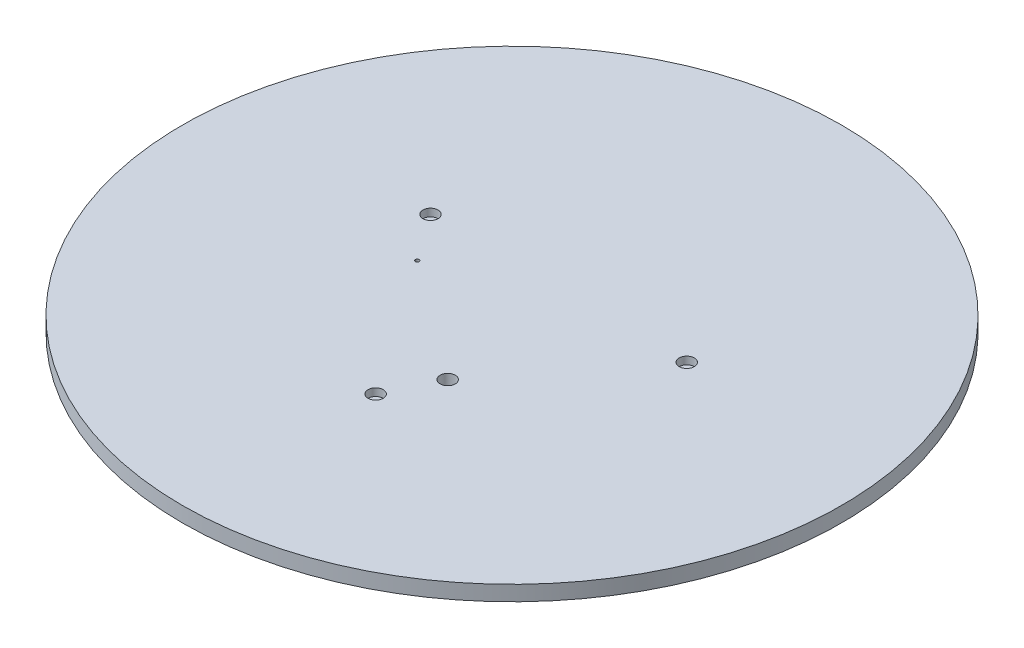
SolidWorks part; units mm, degrees
material "PTFE (general)"
ref_plane "Front Plane" through (0, 0, 0) normal (0, 0, 1) x (1, 0, 0)
ref_plane "Top Plane" through (0, 0, 0) normal (0, 1, 0) x (1, 0, 0)
ref_plane "Right Plane" through (0, 0, 0) normal (1, 0, 0) x (0, 0, -1)
sketch "Sketch1" plane through (0, 0, 0) normal (0, 1, 0) x (1, 0, 0)
  circle A0 centre (0, 0) radius 43.5
  dimension "D2" = 87
extrude "Boss-Extrude1" add sketch "Sketch1" along normal blind 2
sketch "Sketch2" plane through (0, 2, 0) normal (0, 1, 0) x (1, 0, 0)
  line L0 (8.6667, 0) -> (-17.7957, 0) construction
  line L1 (-17.7957, 0) -> (0, 0) construction
  line L2 (-12.5, 0) -> (0, 0) construction
  circle A2 centre (-12.5, 0) radius 0.25
  dimension "D1" = 0.5
  dimension "D2" = 12.5
  dimension "D5" = 0
extrude "Cut-Extrude1" cut sketch "Sketch2" against normal through all both and the other way through all
sketch "Sketch3" plane through (0, 2, 0) normal (0, 1, 0) x (1, 0, 0)
  line L1 (0, 0) -> (0, 12.5) construction
  line L2 (0, 12.5) -> (0, 0) construction
  line L3 (0, 0) -> (7.8426, -29.2691) construction
  circle A1 centre (3.1058, -11.5911) radius 1
  dimension "D3" = 2
  dimension "D4" = 12
  dimension "D5" = 15
extrude "Cut-Extrude2" cut sketch "Sketch3" against normal through all both and the other way through all
sketch "Sketch4" plane through (0, 2, 0) normal (0, 1, 0) x (1, 0, 0)
  line L0 (-16.9145, 6.1564) -> (0, 0) construction
  line L1 (0, 0) -> (0, -18) construction
  line L2 (0, -18) -> (0, 0) construction
  line L3 (0, 0) -> (16.9145, 6.1564) construction
  circle A0 centre (0, 0) radius 18
  circle A1 centre (0, -18) radius 1
  circle A2 centre (-16.9145, 6.1564) radius 1
  circle A3 centre (16.9145, 6.1564) radius 1
  dimension "D1" = 2
  dimension "D2" = 2
  dimension "D3" = 2
  dimension "D4" = 36
  dimension "D5" = 110
  dimension "D6" = 140
extrude "Cut-Extrude3" cut sketch "Sketch4" against normal blind 1 contours A1 | A2 | A3
